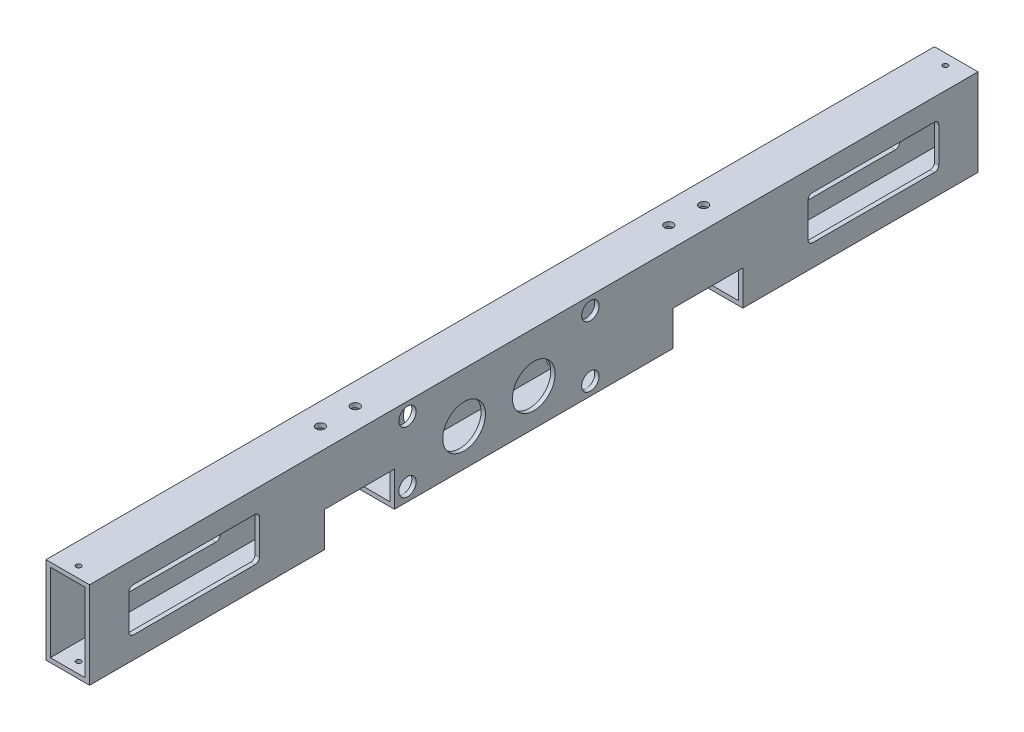
SolidWorks part; units mm, degrees
ref_plane "Front Plane" through (0, 0, 0) normal (0, 0, 1) x (1, 0, 0)
ref_plane "Top Plane" through (0, 0, 0) normal (0, 1, 0) x (1, 0, 0)
ref_plane "Right Plane" through (0, 0, 0) normal (1, 0, 0) x (0, 0, -1)
sketch "Sketch1" plane through (0, 0, 0) normal (0, 0, 1) x (1, 0, 0)
  line L1 (-12.1647, 2.5103) -> (19.5853, 2.5103)
  line L2 (-12.1647, 2.5103) -> (-12.1647, -60.9897)
  line L3 (-12.1647, -60.9897) -> (19.5853, -60.9897)
  line L4 (19.5853, 2.5103) -> (19.5853, -60.9897)
  line L5 (-8.9897, -0.6647) -> (16.4103, -0.6647)
  line L6 (-8.9897, -0.6647) -> (-8.9897, -57.8147)
  line L7 (-8.9897, -57.8147) -> (16.4103, -57.8147)
  line L8 (16.4103, -0.6647) -> (16.4103, -57.8147)
  dimension "D1" = 63.5
  dimension "D2" = 31.75
  dimension "D3" = 3.175
  dimension "D4" = 3.175
  dimension "D5" = 3.175
  dimension "D6" = 3.175
extrude "Boss-Extrude1" add sketch "Sketch1" along normal blind 647.7
sketch "Sketch3" plane through (-12.1647, 0, 0) normal (-1, 0, 0) x (0, 0, 1)
  line L0 (0, 2.5103) -> (0, -60.9897) construction
  line L1 (31.7754, -13.3647) -> (120.6754, -13.3647)
  line L2 (28.6004, -16.5397) -> (28.6004, -41.9397)
  line L3 (31.7754, -45.1147) -> (120.6754, -45.1147)
  line L4 (123.8504, -16.5397) -> (123.8504, -41.9397)
  line L5 (647.7, 2.5103) -> (0, 2.5103) construction
  line L6 (647.7, -60.9897) -> (0, -60.9897) construction
  line L7 (323.85, 2.5103) -> (323.85, -60.9897)
  line L8 (523.8496, -16.5397) -> (523.8496, -41.9397)
  line L9 (615.9246, -45.1147) -> (527.0246, -45.1147)
  line L10 (619.0996, -16.5397) -> (619.0996, -41.9397)
  line L11 (615.9246, -13.3647) -> (527.0246, -13.3647)
  line L12 (647.7, 2.5103) -> (647.7, -60.9897) construction
  line L13 (171.45, -60.9897) -> (222.25, -60.9897)
  line L14 (171.45, -60.9897) -> (171.45, -35.5897)
  line L15 (171.45, -35.5897) -> (222.25, -35.5897)
  line L16 (222.25, -60.9897) -> (222.25, -35.5897)
  line L17 (425.45, -60.9897) -> (476.25, -60.9897)
  line L18 (476.25, -60.9897) -> (476.25, -35.5897)
  line L19 (476.25, -35.5897) -> (425.45, -35.5897)
  line L20 (425.45, -60.9897) -> (425.45, -35.5897)
  arc A0 (28.6004, -41.9397) -> (31.7754, -45.1147) centre (31.7754, -41.9397) ccw
  arc A1 (120.6754, -45.1147) -> (123.8504, -41.9397) centre (120.6754, -41.9397) ccw
  arc A2 (120.6754, -13.3647) -> (123.8504, -16.5397) centre (120.6754, -16.5397) cw
  arc A3 (31.7754, -13.3647) -> (28.6004, -16.5397) centre (31.7754, -16.5397) ccw
  arc A4 (615.9246, -13.3647) -> (619.0996, -16.5397) centre (615.9246, -16.5397) cw
  arc A5 (527.0246, -13.3647) -> (523.8496, -16.5397) centre (527.0246, -16.5397) ccw
  arc A6 (527.0246, -45.1147) -> (523.8496, -41.9397) centre (527.0246, -41.9397) cw
  arc A7 (619.0996, -41.9397) -> (615.9246, -45.1147) centre (615.9246, -41.9397) cw
  line M7 (0, -60.9897) -> (647.7, -60.9897)
  dimension "D5" = 3.175
  dimension "D1" = 28.6004
  dimension "D2" = 15.875
  dimension "D3" = 15.875
  dimension "D4" = 95.25
  dimension "D6" = 25.4
  dimension "D7" = 50.8
  dimension "D8" = 171.45
  dimension "D9" = 50.8
  dimension "D10" = 25.4
  dimension "D11" = 171.45
  dimension "D12" = 203.2
extrude "Cut-Extrude1" cut sketch "Sketch3" against normal up to surface (31.75 mm away) contours L1 A3 L2 A0 L3 A1 L4 A2 | A7 L10 A4 L11 A5 L8 A6 L9 | L16 L15 L14 M7 | L20 L18 L19 M7 region at (-12.1647, -29.2397, 76.2254) region at (-12.1647, -29.2397, 571.4746) region at (-12.1647, -48.2897, 196.85) region at (-12.1647, -48.2897, 450.85) up to face at (19.5853, -29.2397, 323.85)
sketch "Sketch6" plane through (19.5853, 0, 0) normal (1, 0, 0) x (0, 0, -1)
  line L1 (-425.45, -60.9897) -> (-222.25, -60.9897) construction
  line L2 (-415.925, -7.0147) -> (-282.575, -7.0147) construction
  line L3 (-415.925, -7.0147) -> (-415.925, -51.4647) construction
  line L4 (-647.7, -60.9897) -> (-647.7, 2.5103) construction
  line L5 (-415.925, -51.4647) -> (-282.575, -51.4647) construction
  line L6 (-282.575, -7.0147) -> (-282.575, -51.4647) construction
  circle A0 centre (-323.85, -34.0022) radius 15.5575
  circle A1 centre (-374.65, -34.0022) radius 15.5575
  circle A2 centre (-415.925, -7.0147) radius 3.175
  circle A3 centre (-282.575, -7.0147) radius 3.175
  circle A4 centre (-415.925, -51.4647) radius 3.175
  circle A5 centre (-282.575, -51.4647) radius 3.175
  dimension "D1" = 31.115
  dimension "D4" = 50.8
  dimension "D6" = 17.4625
  dimension "D8" = 92.075
  dimension "D7" = 6.35
  dimension "D2" = 26.9875
  dimension "D3" = 323.85
  dimension "D5" = 26.9875
  dimension "D9" = 41.275
extrude "Cut-Extrude2" cut sketch "Sketch6" against normal up to surface (31.75 mm away) up to face at (-12.1647, -41.9397, 323.85)
sketch "Sketch7" plane through (19.5853, 0, 0) normal (1, 0, 0) x (0, 0, -1)
  circle A0 centre (-415.925, -7.0147) radius 6.35
  circle A1 centre (-415.925, -51.4647) radius 6.35
  circle A2 centre (-282.575, -51.4647) radius 6.35
  circle A3 centre (-282.575, -7.0147) radius 6.35
  dimension "D1" = 12.7
extrude "Cut-Extrude3" cut sketch "Sketch7" against normal up to next
sketch "Sketch8" plane through (0, 2.5103, 0) normal (0, 1, 0) x (1, 0, 0)
  line L0 (3.7103, -171.45) -> (3.7103, -476.25) construction
  line L1 (-12.1647, -171.45) -> (19.5853, -171.45) construction
  line L2 (-12.1647, -171.45) -> (-12.1647, -222.25) construction
  line L3 (-12.1647, -222.25) -> (19.5853, -222.25) construction
  line L4 (19.5853, -171.45) -> (19.5853, -222.25) construction
  line L5 (19.5853, -425.45) -> (-12.1647, -425.45) construction
  line L6 (19.5853, -425.45) -> (19.5853, -476.25) construction
  line L7 (19.5853, -476.25) -> (-12.1647, -476.25) construction
  line L8 (-12.1647, -425.45) -> (-12.1647, -476.25) construction
  circle A0 centre (3.7103, -184.15) radius 3.175
  circle A1 centre (3.7103, -209.55) radius 3.175
  circle A2 centre (3.7103, -438.15) radius 3.175
  circle A3 centre (3.7103, -463.55) radius 3.175
  dimension "D5" = 6.35
  dimension "D6" = 12.7
  dimension "D7" = 25.4
  dimension "D8" = 12.7
  dimension "D9" = 25.4
  dimension "D1" = 50.8
  dimension "D2" = 31.75
  dimension "D3" = 50.8
  dimension "D4" = 31.75
extrude "Cut-Extrude4" cut sketch "Sketch8" against normal through all
sketch "Sketch9" plane through (0, 2.5103, 0) normal (0, 1, 0) x (1, 0, 0)
  line L0 (19.5853, 0) -> (-12.1647, 0) construction
  line L1 (-12.1647, -647.7) -> (-12.1647, 0) construction
  line L2 (19.5853, -647.7) -> (-12.1647, -647.7) construction
  circle A0 centre (3.7103, -639.7625) radius 1.8415
  circle A1 centre (3.7103, -7.9375) radius 1.8415
  dimension "D1" = 3.683
  dimension "D4" = 3.683
  dimension "D2" = 7.9375
  dimension "D3" = 15.875
  dimension "D5" = 7.9375
  dimension "D6" = 15.875
extrude "Cut-Extrude5" cut sketch "Sketch9" against normal up to surface (63.5 mm away) up to face at (3.7103, -60.9897, 561.975)
